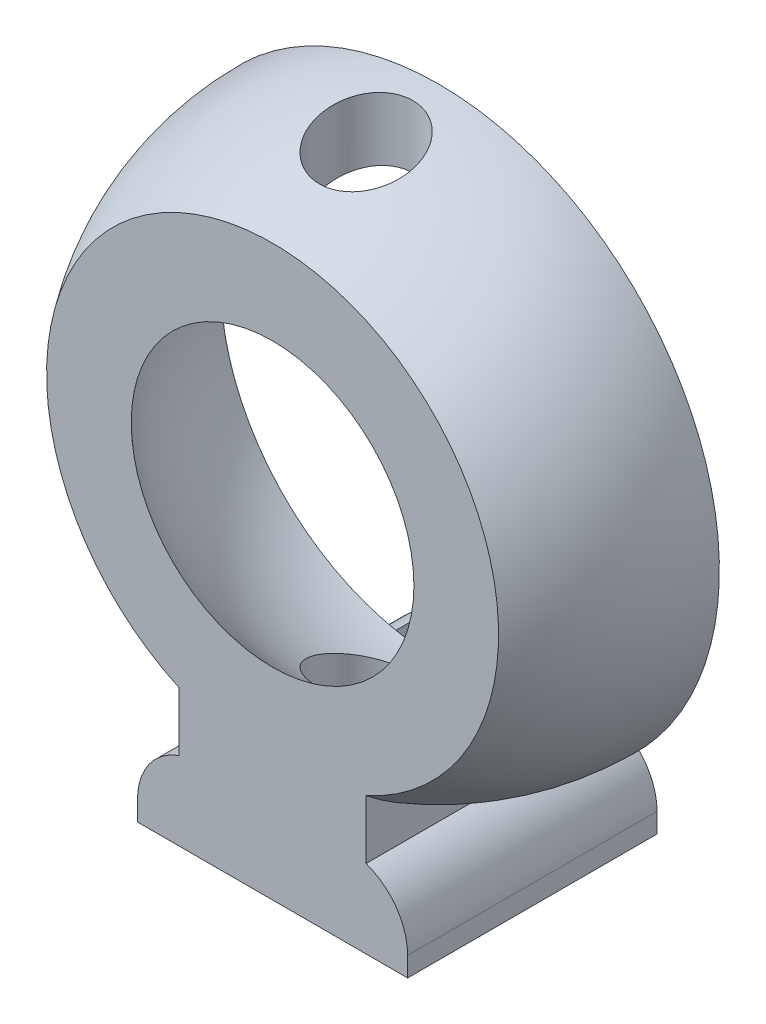
SolidWorks part; units mm, degrees
ref_plane "Front Plane" through (0, 0, 0) normal (0, 0, 1) x (1, 0, 0)
ref_plane "Top Plane" through (0, 0, 0) normal (0, 1, 0) x (1, 0, 0)
ref_plane "Right Plane" through (0, 0, 0) normal (1, 0, 0) x (0, 0, -1)
sketch "Sketch4" plane through (0, 60.25, 0) normal (0, 1, 0) x (1, 0, 0)
  line L0 (-103.35, -1.5487) -> (10.75, -1.5487) construction
  line L1 (-7.75, 16.4513) -> (1.25, 16.4513)
  line L2 (-7.75, 16.4513) -> (-7.75, 0.4513)
  line L3 (-7.75, 0.4513) -> (1.25, 0.4513)
  line L4 (1.25, 16.4513) -> (1.25, 0.4513)
  line L5 (1.25, 6) -> (1.25, 1.5) construction
  line L6 (-5.75, 4.9513) -> (-7.75, 4.9513) construction
  line L7 (-3.25, 2.4513) -> (-3.25, 0.4513) construction
  line L8 (-3.25, 9.4513) -> (-3.25, 7.4513) construction
  line L9 (-0.75, 4.9513) -> (1.25, 4.9513) construction
  line L11 (-3.25, 14.4513) -> (-3.25, 16.4513) construction
  line L12 (-38.5, -1.5487) -> (38.5, -1.5487) construction
  line L13 (-7.75, 16.4513) -> (1.25, 16.4513)
  line L14 (-7.75, 16.4513) -> (-7.75, 8.4513)
  line L15 (-7.75, 8.4513) -> (1.25, 8.4513)
  line L16 (1.25, 16.4513) -> (1.25, 8.4513)
  line L17 (1.25, 8.4513) -> (-7.75, 8.4513)
  line L18 (1.25, 8.4513) -> (1.25, 0.4513)
  line L19 (1.25, 0.4513) -> (-7.75, 0.4513)
  line L20 (-7.75, 8.4513) -> (-7.75, 0.4513)
  circle A0 centre (-3.25, 4.9513) radius 2.5 construction
  circle A1 centre (-3.25, 11.9513) radius 1.25
  circle A2 centre (-3.25, 8.4513) radius 10 construction
  circle A3 centre (-3.25, 4.9513) radius 1.25
  circle A4 centre (-3.25, 11.9513) radius 2.5 construction
  point P26 (-3.25, 8.4513)
  circle M37 centre (-3.25, 4.9513) radius 1.25
  dimension "D1" = 20
  dimension "D2" = 5
  dimension "D5" = 2.5
  dimension "D3" = 2
extrude "BaseBoss" add sketch "Sketch4" along normal blind 3 contours A0 | A4 | L15 L2 L3 L4 M37 region at (-3.25, 60.25, -8.3308)
ref_plane "RevolveSketchPlane" through (-3.25, 0, 0) normal (-1, 0, 0) x (0, 0, 1)
sketch "Sketch5" plane through (-3.25, 0, 0) normal (-1, 0, 0) x (0, 0, 1)
  line L0 (-8.4513, 63.25) -> (-8.4513, 66.25)
  line L2 (-8.4513, 63.25) -> (-0.4513, 63.25) construction
  line L3 (-8.4513, 63.25) -> (-0.4513, 63.25) construction
  line L4 (-0.4513, 76.75) -> (-8.4513, 76.75) construction
  line L5 (-0.4513, 63.25) -> (-0.4513, 60.25) construction
  line L7 (-0.4513, 63.25) -> (-0.4513, 60.25) construction
  line L8 (-0.4513, 65.8757) -> (-0.4513, 69.9493)
  arc A0 (-8.4513, 63.25) -> (-0.4513, 65.8757) centre (-8.4513, 76.75) ccw
  arc A1 (-8.4513, 66.25) -> (-0.4513, 69.9493) centre (-8.4513, 76.75) ccw
  point P4 (-0.4513, 76.75)
  point P5 (0, 0)
  point P7 (0, 0)
  point P9 (0, 0)
  dimension "D1" = 21
  dimension "D2" = 3
revolve "CoverRevolve" add sketch "Sketch5" angle 360 about L4
extrude "Boss-Extrude3" add sketch "Sketch4<5>" along normal up to surface (7.1358 mm away) contours L15 L2 L3 L4 M37 region at (-3.25, 60.25, -8.3308) up to face at (7.25, 76.75, -8.4513)
sketch "Sketch4<5>" plane through (0, 60.25, 0) normal (0, 1, 0) x (1, 0, 0) same geometry as "Sketch4"
ref_plane "BasePlane" through (0, 63.25, 0) normal (0, -1, 0) x (-1, 0, 0)
sketch "Sketch6" plane through (0, 63.25, 0) normal (0, -1, 0) x (-1, 0, 0)
  circle A5 centre (3.25, 4.9513) radius 2.25
  circle A6 centre (3.25, 4.9513) radius 2.25
  dimension "D1" = 1
extrude "Cut-Extrude1" cut sketch "Sketch6" against normal through all contours A6
sketch "Sketch7" plane through (1.25, 0, 0) normal (1, 0, 0) x (0, 0, -1)
  line L1 (0.4513, 60.25) -> (12.4513, 60.25)
  line L2 (0.4513, 60.25) -> (0.4513, 64.0221)
  line L3 (0.4513, 64.0221) -> (12.4513, 64.0221)
  line L4 (12.4513, 60.25) -> (12.4513, 64.0221)
  line L6 (12.4513, 60.25) -> (16.4513, 60.25) construction
  line L7 (12.4513, 62.136) -> (8.4513, 62.136) construction
  line L8 (8.4513, 64.0221) -> (8.4513, 60.25) construction
  point P5 (0, 0)
  point P9 (0, 0)
extrude "Boss-Extrude4" add sketch "Sketch7" along normal blind 2
fillet "Fillet1" radius 3 1 edges at (3.25, 64.0221, -6.4513)
mirror "Mirror1" about plane through (-3.25, 0, 0) normal (-1, 0, 0) of "Fillet1", "Boss-Extrude4"
equation "\"D5@Sketch4\"=3-.5"
equation "\"D1@Sketch5\"=2*(10+.5)"
